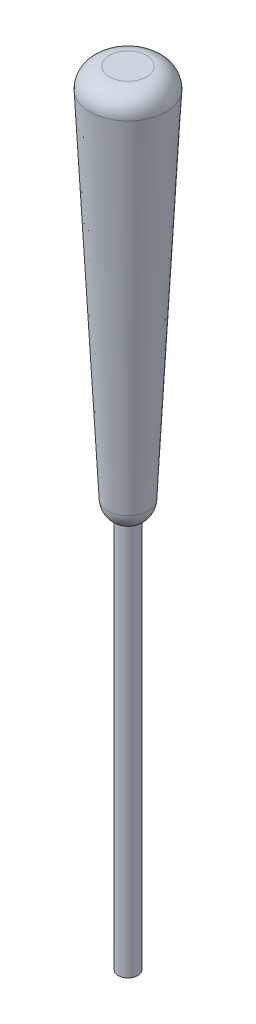
SolidWorks part; units mm, degrees
ref_plane "Front Plane" through (0, 0, 0) normal (0, 0, 1) x (1, 0, 0)
ref_plane "Top Plane" through (0, 0, 0) normal (0, 1, 0) x (1, 0, 0)
ref_plane "Right Plane" through (0, 0, 0) normal (1, 0, 0) x (0, 0, -1)
sketch "Sketch1" plane through (0, 0, 0) normal (0, 1, 0) x (1, 0, 0)
  circle A0 centre (0, 0) radius 2.5
  dimension "D1" = 5
extrude "Boss-Extrude1" add sketch "Sketch1" along normal blind 100
sketch "Sketch2" plane through (0, 100, 0) normal (0, 1, 0) x (1, 0, 0)
  circle A0 centre (0, 0) radius 5
  dimension "D1" = 10
ref_plane "Plane1" through (0, 200, 0) normal (0, 1, 0) x (1, 0, 0)
sketch "Sketch3" plane through (0, 200, 0) normal (0, 1, 0) x (1, 0, 0)
  circle A0 centre (0, 0) radius 10
  dimension "D1" = 20
loft "Loft1" add profiles "Sketch3", "Sketch2" connector at (-0.0807, 200, 9.9997) connector at (-0.5705, 100, 4.9673)
fillet "Fillet1" radius 5 2 edges at (0, 200, 10) (0, 100, 5)
